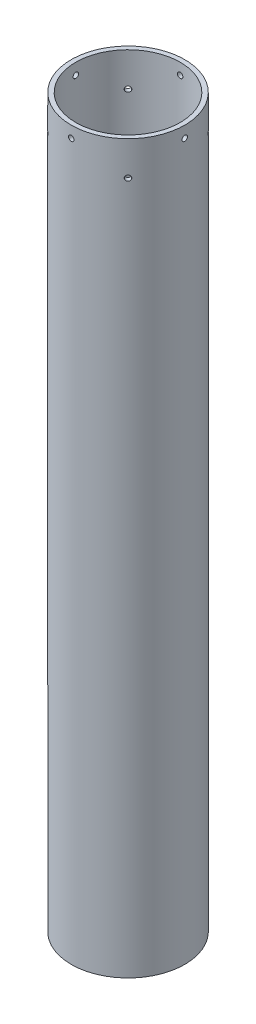
SolidWorks part; units mm, degrees
material "ПВХ 0.007 Смягченный"
ref_plane "Спереди" through (0, 0, 0) normal (0, 0, 1) x (1, 0, 0)
ref_plane "Сверху" through (0, 0, 0) normal (0, 1, 0) x (1, 0, 0)
ref_plane "Справа" through (0, 0, 0) normal (1, 0, 0) x (0, 0, -1)
sketch "Эскиз1" plane through (0, 0, 0) normal (0, 1, 0) x (1, 0, 0)
  circle A0 centre (0, 0) radius 25
  circle A1 centre (0, 0) radius 23
  dimension "ExDBody" = 50
  dimension "InDBody" = 46
extrude "Бобышка-Вытянуть1" add sketch "Эскиз1" along normal blind 320
sketch "Эскиз2" plane through (0, 0, 0) normal (1, 0, 0) x (0, 0, -1)
  line L0 (23, 320) -> (-23, 320) construction
  circle A0 centre (0, 315) radius 1.2
  dimension "D1" = 5
  dimension "D2" = 2.4
extrude "Вырез-Вытянуть1" cut sketch "Эскиз2" against normal through all
pattern_circular "Круговой массив1" count 4 over 360 about axis through (0, 320, 0) along (0, -1, 0) of "Вырез-Вытянуть1"
ref_plane "Плоскость1" through (0, 0, 0) normal (-0.7071, 0, 0.7071) x (0, -1, 0)
sketch "Эскиз3" plane through (0, 0, 0) normal (-0.7071, 0, 0.7071) x (0, -1, 0)
  line L0 (-320, 0) -> (0, 0) construction
  line L1 (-320, 25) -> (-320, -25) construction
  circle A0 centre (-305, 0) radius 1.2
  dimension "D1" = 2.4
  dimension "D2" = 15
extrude "Вырез-Вытянуть2" cut sketch "Эскиз3" against normal through all
pattern_circular "Круговой массив2" count 4 over 360 about axis through (0, 320, 0) along (0, -1, 0) of "Вырез-Вытянуть2"
